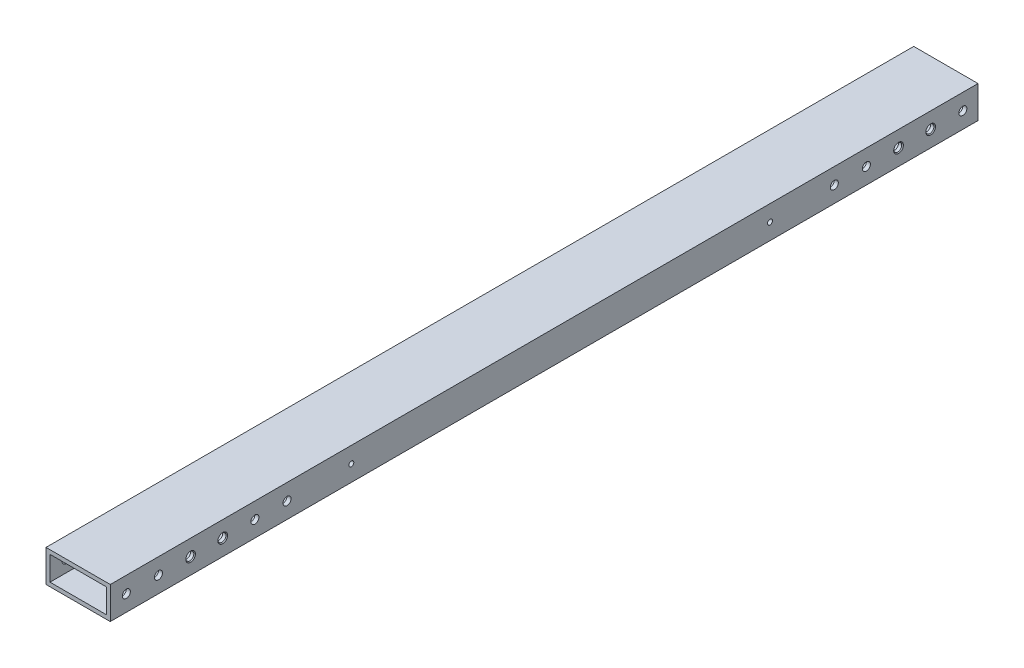
SolidWorks part; units mm, degrees
material "6061 Alloy"
ref_plane "Front Plane" through (0, 0, 0) normal (0, 0, 1) x (1, 0, 0)
ref_plane "Top Plane" through (0, 0, 0) normal (0, 1, 0) x (1, 0, 0)
ref_plane "Right Plane" through (0, 0, 0) normal (1, 0, 0) x (0, 0, -1)
sketch "Sketch1" plane through (0, 0, 0) normal (0, 0, 1) x (1, 0, 0)
  line L0 (-22.225, 9.525) -> (22.225, 9.525)
  line L2 (-25.4, 12.7) -> (25.4, 12.7)
  line L3 (-25.4, 12.7) -> (-25.4, -12.7)
  line L4 (-25.4, -12.7) -> (25.4, -12.7)
  line L5 (25.4, 12.7) -> (25.4, -12.7)
  line L10 (22.225, 9.525) -> (22.225, -9.525)
  line L11 (-22.225, -9.525) -> (22.225, -9.525)
  line L12 (-22.225, 9.525) -> (-22.225, -9.525)
  point P12 (0, 12.7)
  point P14 (25.4, 0)
  dimension "Wall Thickness" = 3.175
  dimension "Outside Width" = 50.8
  dimension "Outside Height" = 25.4
  dimension "Inside Height" = 19.05
  dimension "Inside Width" = 44.45
sketch "Sketch2" plane through (0, 0, 0) normal (1, 0, 0) x (0, 0, -1)
  line L0 (342.9, 0) -> (-342.9, 0)
  point P4 (0, 0)
  point P7 (-342.9, 0)
  point P10 (342.9, 0)
  dimension "Length" = 685.8
sketch "Sketch3" plane through (0, 0, 0) normal (0, 0, 1) x (1, 0, 0)
  line L21 (25.4, 12.7) -> (-25.4, 12.7)
  line L22 (25.4, -12.7) -> (25.4, 12.7)
  line L23 (-25.4, -12.7) -> (25.4, -12.7)
  line L24 (-25.4, 12.7) -> (-25.4, -12.7)
  line L25 (25.4, 12.7) -> (-25.4, 12.7)
  line L26 (25.4, -12.7) -> (25.4, 12.7)
  line L27 (-25.4, -12.7) -> (25.4, -12.7)
  line L28 (-25.4, 12.7) -> (-25.4, -12.7)
  line L29 (22.225, 9.525) -> (-22.225, 9.525)
  line L30 (22.225, -9.525) -> (22.225, 9.525)
  line L31 (-22.225, -9.525) -> (22.225, -9.525)
  line L32 (-22.225, 9.525) -> (-22.225, -9.525)
  line L33 (22.225, 9.525) -> (-22.225, 9.525)
  line L34 (22.225, -9.525) -> (22.225, 9.525)
  line L35 (-22.225, -9.525) -> (22.225, -9.525)
  line L36 (-22.225, 9.525) -> (-22.225, -9.525)
  dimension "D1" = 0
  dimension "D2" = 0
extrude "Boss-Extrude1" add sketch "Sketch3" along normal up to vertex (342.9 mm away) and the other way up to vertex (342.9 mm away) up to point (0, 0, 342.9) other way up to point (0, 0, -342.9)
sketch "Drawing Reference" plane through (0, 0, 0) normal (1, 0, 0) x (0, 0, -1)
  line L0 (-342.9, 0) -> (342.9, 0) construction
  line L1 (0, -12.7) -> (0, 12.7) construction
  line L2 (-342.9, -12.7) -> (342.9, -12.7) construction
  line L5 (-342.9, 12.7) -> (342.9, 12.7) construction
  point P7 (-306.324, 0)
  point P8 (306.324, 0)
  dimension "D1" = 36.576
sketch "Sketch5" plane through (25.4, 0, 0) normal (1, 0, 0) x (0, 0, -1)
  line L0 (-342.9, 0) -> (-279.4, 0)
  line L1 (-342.9, -12.7) -> (-342.9, 12.7) construction
  line L2 (-279.4, 0) -> (-254, 0)
  line L3 (-254, 0) -> (-228.6, 0)
  line L4 (-228.6, 0) -> (-203.2, 0)
sketch "Sketch8" plane through (25.4, 0, 0) normal (1, 0, 0) x (0, 0, -1)
  line L0 (342.9, 0) -> (305.5118, 0)
  line L1 (342.9, -12.7) -> (342.9, 12.7) construction
  line L2 (305.5118, 0) -> (280.1118, 0)
  line L3 (280.1118, 0) -> (254.7118, 0)
  line L4 (254.7118, 0) -> (229.3118, 0)
  point P5 (0, 0)
hole_wizard "1/4 (0.25) Diameter Hole3" positions "Sketch12" profile "Sketch13" hole size "1/4" standard "ANSI Inch" end condition through all
sketch "Sketch12" plane through (-25.4, 0, 0) normal (-1, 0, 0) x (0, 0, 1)
  point P0 (-330.9118, 0)
sketch "Sketch13" plane through (-25.4, 0, -330.9118) normal (0, 1, 0) x (0, 0, 1)
  line L0 (0, 0) -> (0, 50.8)
  line L1 (0, 50.8) -> (3.175, 50.8)
  line L2 (3.175, 50.8) -> (3.175, 0)
  line L5 (3.175, 0) -> (0, 0)
  line L11 (0, -6.35) -> (0, 107.95) construction
  dimension "Thru Hole Dia." = 6.35
  dimension "Thru Hole Depth" = 50.8
hole_wizard "1/4 (0.25) Diameter Hole4" positions "Sketch14" profile "Sketch15" hole size "1/4" standard "ANSI Inch" end condition through all
sketch "Sketch14" plane through (-25.4, 0, 0) normal (-1, 0, 0) x (0, 0, 1)
  point P0 (304.8, 0)
  point P3 (330.2, 0)
sketch "Sketch15" plane through (-25.4, 0, 304.8) normal (0, 1, 0) x (0, 0, 1)
  line L0 (0, 0) -> (0, 50.8)
  line L1 (0, 50.8) -> (3.175, 50.8)
  line L2 (3.175, 50.8) -> (3.175, 0)
  line L5 (3.175, 0) -> (0, 0)
  line L11 (0, -6.35) -> (0, 107.95) construction
  dimension "Thru Hole Dia." = 6.35
  dimension "Thru Hole Depth" = 50.8
hole_wizard "1/4 (0.25) Diameter Hole5" positions "Sketch17" profile "Sketch18" hole size "1/4" standard "ANSI Inch" end condition through all
sketch "Sketch17" plane through (25.4, 0, 0) normal (1, 0, 0) x (0, 0, -1)
  point P0 (305.5118, 0)
  point P3 (280.1118, 0)
sketch "Sketch18" plane through (25.4, 0, -305.5118) normal (0, 1, 0) x (0, 0, -1)
  line L0 (0, 0) -> (0, 50.8)
  line L1 (0, 50.8) -> (3.175, 50.8)
  line L2 (3.175, 50.8) -> (3.175, 0.6604)
  line L3 (3.175, 0.6604) -> (3.8354, 0)
  line L5 (3.8354, 0) -> (0, 0)
  line L6 (-3.175, 0.6604) -> (-3.8354, 0) construction
  line L11 (0, -6.35) -> (0, 107.95) construction
  dimension "Thru Hole Dia." = 6.35
  dimension "Thru Hole Depth" = 50.8
  dimension "Near C'Sink Dia." = 7.6708
  dimension "Near C'Sink Angle" = 90
hole_wizard "1/4 (0.25) Diameter Hole6" positions "Sketch19" profile "Sketch20" hole size "1/4" standard "ANSI Inch" end condition through all
sketch "Sketch19" plane through (25.4, 0, 0) normal (1, 0, 0) x (0, 0, -1)
  point P0 (229.3118, 0)
  point P3 (254.7118, 0)
sketch "Sketch20" plane through (25.4, 0, -229.3118) normal (0, 1, 0) x (0, 0, -1)
  line L0 (0, 0) -> (0, 50.8)
  line L1 (0, 50.8) -> (3.175, 50.8)
  line L2 (3.175, 50.8) -> (3.175, 0)
  line L5 (3.175, 0) -> (0, 0)
  line L11 (0, -6.35) -> (0, 107.95) construction
  dimension "Thru Hole Dia." = 6.35
  dimension "Thru Hole Depth" = 50.8
hole_wizard "1/4 (0.25) Diameter Hole7" positions "Sketch21" profile "Sketch22" hole size "1/4" standard "ANSI Inch" end condition through all
sketch "Sketch21" plane through (25.4, 0, 0) normal (1, 0, 0) x (0, 0, -1)
  point P0 (-203.2, 0)
  point P3 (-228.6, 0)
sketch "Sketch22" plane through (25.4, 0, 203.2) normal (0, 1, 0) x (0, 0, -1)
  line L0 (0, 0) -> (0, 50.8)
  line L1 (0, 50.8) -> (3.175, 50.8)
  line L2 (3.175, 50.8) -> (3.175, 0)
  line L5 (3.175, 0) -> (0, 0)
  line L11 (0, -6.35) -> (0, 107.95) construction
  dimension "Thru Hole Dia." = 6.35
  dimension "Thru Hole Depth" = 50.8
hole_wizard "1/4 (0.25) Diameter Hole8" positions "Sketch23" profile "Sketch24" hole size "1/4" standard "ANSI Inch" end condition through all
sketch "Sketch23" plane through (25.4, 0, 0) normal (1, 0, 0) x (0, 0, -1)
  point P0 (-279.4, 0)
  point P3 (-254, 0)
sketch "Sketch24" plane through (25.4, 0, 279.4) normal (0, 1, 0) x (0, 0, -1)
  line L0 (0, 0) -> (0, 50.8)
  line L1 (0, 50.8) -> (3.175, 50.8)
  line L2 (3.175, 50.8) -> (3.175, 0.6604)
  line L3 (3.175, 0.6604) -> (3.8354, 0)
  line L5 (3.8354, 0) -> (0, 0)
  line L6 (-3.175, 0.6604) -> (-3.8354, 0) construction
  line L11 (0, -6.35) -> (0, 107.95) construction
  dimension "Thru Hole Dia." = 6.35
  dimension "Thru Hole Depth" = 50.8
  dimension "Near C'Sink Dia." = 7.6708
  dimension "Near C'Sink Angle" = 90
sketch "Sketch25" plane through (25.4, 0, 0) normal (1, 0, 0) x (0, 0, -1)
  line L0 (-203.2, 0) -> (-152.4, 0)
  line L1 (229.3118, 0) -> (178.5118, 0)
hole_wizard "5/32 (0.15625) Diameter Hole1" positions "Sketch26" profile "Sketch27" hole size "5/32" standard "ANSI Inch" end condition through all
sketch "Sketch26" plane through (25.4, 0, 0) normal (1, 0, 0) x (0, 0, -1)
  point P0 (-152.4, 0)
  point P3 (178.5118, 0)
sketch "Sketch27" plane through (25.4, 0, 152.4) normal (0, 1, 0) x (0, 0, -1)
  line L0 (0, 0) -> (0, 50.8)
  line L1 (0, 50.8) -> (1.9844, 50.8)
  line L2 (1.9844, 50.8) -> (1.9844, 0)
  line L5 (1.9844, 0) -> (0, 0)
  line L11 (0, -6.35) -> (0, 107.95) construction
  dimension "Thru Hole Dia." = 3.9688
  dimension "Thru Hole Depth" = 50.8
equation "\"D1@Drawing Reference\"=\"Outside Width@Sketch1\" * 0.72"
